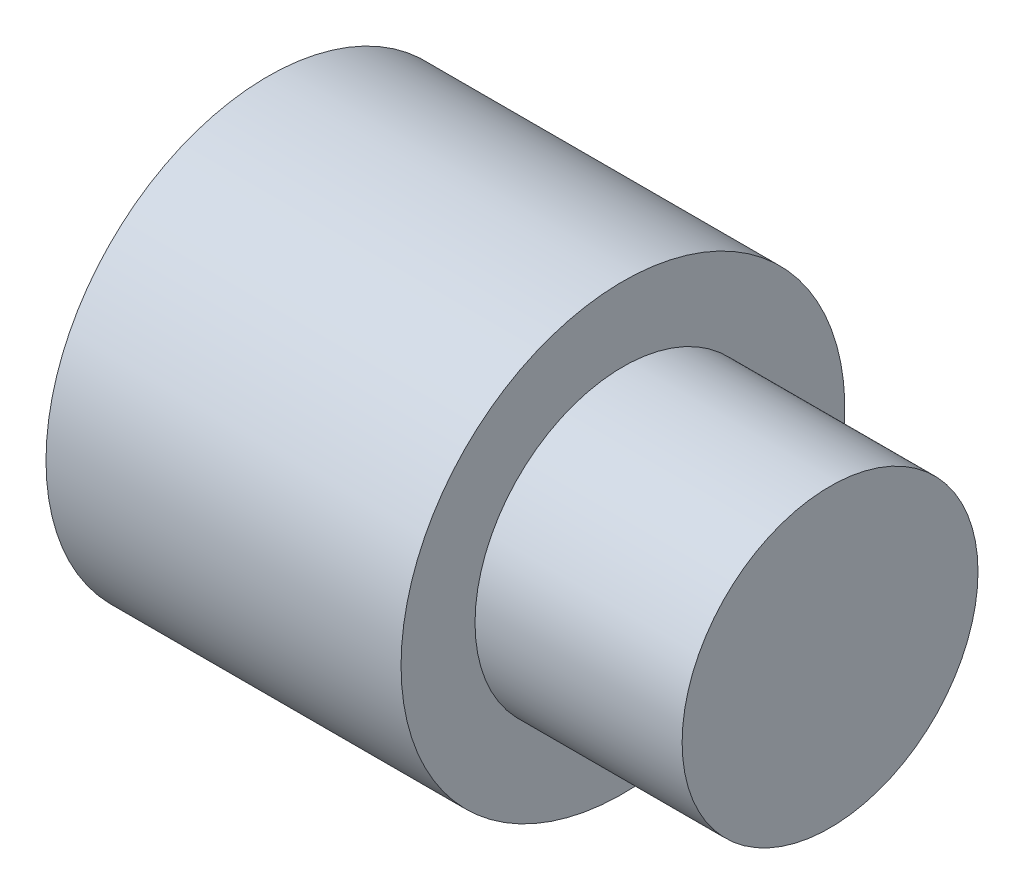
SolidWorks part; units mm, degrees
ref_plane "Front Plane" through (0, 0, 0) normal (0, 0, 1) x (1, 0, 0)
ref_plane "Top Plane" through (0, 0, 0) normal (0, 1, 0) x (1, 0, 0)
ref_plane "Right Plane" through (0, 0, 0) normal (1, 0, 0) x (0, 0, -1)
sketch "Reg_Outlet_Upper Sketch" plane through (0, 0, 0) normal (0, 0, 1) x (1, 0, 0)
  line L0 (-1000, 0) -> (1000, 0) construction
  line L1 (14, 0) -> (14, 10)
  line L2 (14, 10) -> (0, 10)
  line L3 (0, 10) -> (0, 15)
  line L4 (0, 15) -> (-24, 15)
  line L5 (-24, 15) -> (-24, 0)
  line L6 (-24, 0) -> (14, 0)
revolve "Reg_Outlet_Upper" add sketch "Reg_Outlet_Upper Sketch" angle 360 about L0
ref_axis "Engine Axis" through (15.9, 0, 0) along (-1, 0, 0)
sketch "Socket 1 Sketch" plane through (0, 0, 0) normal (0, 0, 1) x (1, 0, 0)
  line L0 (-1000, 0) -> (1000, 0) construction
  line L1 (-25, 0) -> (-25, 4.953)
  line L2 (-25, 4.953) -> (-13.5, 4.953)
  line L3 (-13.5, 4.953) -> (-13.5, 0)
  line L4 (-13.5, 0) -> (-25, 0)
revolve "Socket 1" cut sketch "Socket 1 Sketch" angle 360 about L0
